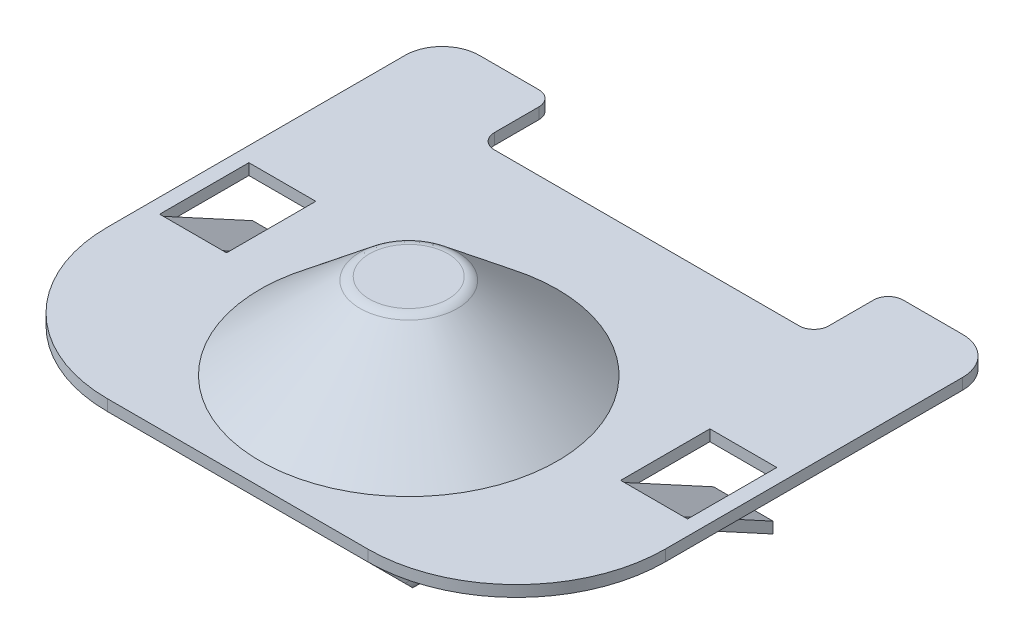
SolidWorks part; units mm, degrees
material "Plain Carbon Steel"
ref_plane "Front Plane" through (0, 0, 0) normal (0, 0, 1) x (1, 0, 0)
ref_plane "Top Plane" through (0, 0, 0) normal (0, 1, 0) x (1, 0, 0)
ref_plane "Right Plane" through (0, 0, 0) normal (1, 0, 0) x (0, 0, -1)
sketch "Sketch1" plane through (0, 0, 0) normal (0, 1, 0) x (1, 0, 0)
  line L1 (-7.5, 6.5) -> (7.5, 6.5)
  line L2 (-7.5, 6.5) -> (-7.5, -6.5)
  line L3 (-7.5, -6.5) -> (7.5, -6.5)
  line L4 (7.5, 6.5) -> (7.5, -6.5)
  line L5 (-7.5, 6.5) -> (7.5, -6.5) construction
  line L6 (-7.5, -6.5) -> (7.5, 6.5) construction
  point P0 (0, 0)
  dimension "D1" = 15
  dimension "D2" = 13
extrude "BASE" add sketch "Sketch1" along normal blind 0.3
sketch "Sketch2" plane through (0, 0.3, 0) normal (0, 1, 0) x (1, 0, 0)
  line L1 (0, -6.5) -> (0, -1.9) construction
  line L2 (-7.5, -6.5) -> (7.5, -6.5) construction
  circle A0 centre (0, -1.9) radius 4
  dimension "D1" = 8
  dimension "D3" = 4.6
extrude "PT CUT" cut sketch "Sketch2" against normal through all
ref_axis "POSITIVE" through (0, 0, 1.9) along (0, 1, 0)
ref_plane "PT REFERENCE PLANE" through (0, 0, 1.9) normal (0, 0, 1) x (1, 0, 0)
sketch "Sketch4" plane through (0, 0, 1.9) normal (0, 0, 1) x (1, 0, 0)
  line L0 (0, 2.6) -> (1.0568, 2.6)
  line L2 (4, 0) -> (3.7, 0)
  line L4 (1.0936, 2.3) -> (0, 2.3)
  line L5 (0, 2.3) -> (0, 2.6)
  line L6 (-4, 0) -> (4, 0) construction
  line L7 (4, 0) -> (4, 0.3) construction
  line L8 (1.3107, 2.5091) -> (4, 0.3)
  line L9 (4, 0.3) -> (-4, 0.3) construction
  line L10 (4, 0) -> (4, 0.3)
  line L11 (0, 0) -> (0, 0.3) construction
  line L12 (3.6, 0.1) -> (3.6, 0.2527)
  line L13 (3.5635, 0.33) -> (1.2206, 2.2545)
  line L14 (-7.5, 0) -> (7.5, 0) construction
  line L15 (3.6, 0.3) -> (4, 0.3) construction
  arc A0 (1.0936, 2.3) -> (1.2206, 2.2545) centre (1.0936, 2.1) cw
  arc A1 (1.3107, 2.5091) -> (1.0568, 2.6) centre (1.0568, 2.2) ccw
  arc A2 (3.6, 0.1) -> (3.7, 0) centre (3.7, 0.1) ccw
  arc A3 (3.5635, 0.33) -> (3.6, 0.2527) centre (3.5, 0.2527) cw
  point P22 (1.2, 2.6)
  dimension "D4" = 0.2
  dimension "D5" = 0.4
  dimension "D6" = 0.1
  dimension "D7" = 0.1
  dimension "D1" = 0.3
  dimension "D2" = 1.2
  dimension "D3" = 2.6
revolve "POSITIVE TERMINAL" add sketch "Sketch4" angle 360 about axis through (0, 0, 1.9) along (0, 1, 0)
sketch "Sketch5" plane through (0, 0, 0) normal (1, 0, 0) x (0, 0, -1)
  line L0 (-6.5, 0) -> (-2.5, -4)
  line L1 (-6.5, 0.3) -> (-6.5, 0) construction
  line L2 (-6.5, 0) -> (-6.2, 0)
  line L3 (-6.2, 0) -> (-2.2, -4)
  line L4 (-2.2, -4) -> (-2.5, -4)
  dimension "D1" = 45
  dimension "D2" = 4
  dimension "D3" = 0.3
extrude "WIRE CONNECTION" add sketch "Sketch5" along normal mid plane 2
sketch "Sketch7" plane through (0, 0.3, 0) normal (0, 1, 0) x (1, 0, 0)
  line L0 (-7.5, -6.5) -> (7.5, -6.5) construction
  line L1 (5.3, 0.9) -> (7.1, 0.9)
  line L2 (5.3, 0.9) -> (5.3, -1.5)
  line L3 (5.3, -1.5) -> (7.1, -1.5)
  line L4 (7.1, 0.9) -> (7.1, -1.5)
  line L5 (5.3, 0.9) -> (7.1, -1.5) construction
  line L6 (5.3, -1.5) -> (7.1, 0.9) construction
  line L7 (7.5, -6.5) -> (7.5, 6.5) construction
  point P0 (6.2, -0.3)
  dimension "D1" = 2.4
  dimension "D2" = 1.8
  dimension "D3" = 5
  dimension "D4" = 0.4
extrude "LOCKING CLAMP CUT" cut sketch "Sketch7" against normal through all
ref_plane "LCC REFERENCE PLANE" through (6.2, 0, 0) normal (1, 0, 0) x (0, 0, -1)
sketch "Sketch8" plane through (6.2, 0, 0) normal (1, 0, 0) x (0, 0, -1)
  line L0 (0.9, -1) -> (-1.5, 0.3)
  line L1 (-1.5, 0.3) -> (-1.5, 0)
  line L2 (-1.5, 0) -> (0.9, -1.3)
  line L3 (0.9, -1.3) -> (0.9, -1)
  line L4 (0.9, 0) -> (0.9, 0.3) construction
  point P4 (-1.5, 0)
  point P8 (-1.5, -0.0175)
  point P9 (-1.5, -0.2226)
  point P10 (0, 0)
  dimension "D1" = 1.6
extrude "LOCKING CLAMP" add sketch "Sketch8" along normal mid plane 1.6
mirror "LC M" about plane through (0, 0, 0) normal (1, 0, 0) of "LOCKING CLAMP", "LOCKING CLAMP CUT"
sketch "Sketch9" plane through (0, 0.3, 0) normal (0, 1, 0) x (1, 0, 0)
  line L0 (7.5, 6.5) -> (-7.5, 6.5) construction
  line L1 (-4.5, 4.5) -> (4.5, 4.5)
  line L2 (-4.5, 4.5) -> (-4.5, 6.5)
  line L3 (-4.5, 6.5) -> (4.5, 6.5)
  line L4 (4.5, 4.5) -> (4.5, 6.5)
  line L5 (-4.5, 4.5) -> (4.5, 6.5) construction
  line L6 (-4.5, 6.5) -> (4.5, 4.5) construction
  line L7 (0, 0) -> (0, 5.5) construction
  point P0 (0, 5.5)
  dimension "D1" = 9
  dimension "D2" = 2
extrude "BOTTOM SLOT CUT" cut sketch "Sketch9" against normal through all
fillet "TS F" radius 1 2 edges at (-7.5, 0.15, -6.5) (7.5, 0.15, -6.5)
fillet "BS F" radius 4 2 edges at (7.5, 0.15, 6.5) (-7.5, 0.15, 6.5)
fillet "WC F" radius 0.5 2 edges at (-1, -4, 2.35) (1, -4, 2.35)
fillet "BSC F" radius 0.4 4 edges at (4.5, 0.15, -6.5) (4.5, 0.15, -4.5) (-4.5, 0.15, -4.5) (-4.5, 0.15, -6.5)
